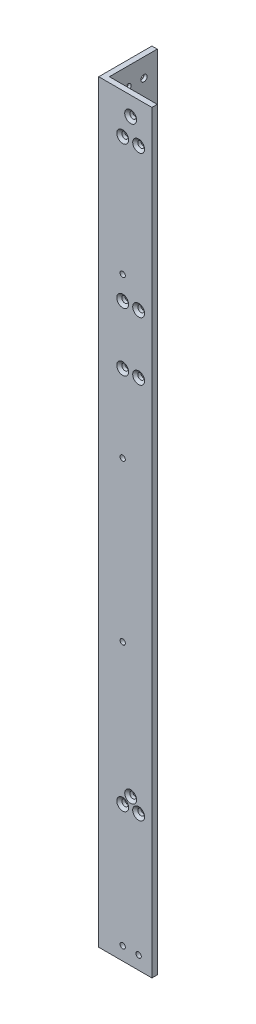
SolidWorks part; units mm, degrees
ref_plane "Front Plane" through (0, 0, 0) normal (0, 0, 1) x (1, 0, 0)
ref_plane "Top Plane" through (0, 0, 0) normal (0, 1, 0) x (1, 0, 0)
ref_plane "Right Plane" through (0, 0, 0) normal (1, 0, 0) x (0, 0, -1)
sketch "Sketch2" plane through (0, 0, 0) normal (0, 1, 0) x (1, 0, 0)
  line L0 (0, 31.75) -> (3.175, 31.75)
  line L1 (3.175, 31.75) -> (3.175, 3.175)
  line L2 (3.175, 3.175) -> (31.75, 3.175)
  line L3 (31.75, 3.175) -> (31.75, 0)
  line L4 (31.75, 0) -> (0, 0)
  line L5 (0, 0) -> (0, 31.75)
  point P9 (1.5875, 31.75)
  point P10 (31.75, 1.5875)
  dimension "D4" = 3.175
  dimension "D1" = 31.75
  dimension "D2" = 31.75
  dimension "D3" = 3.175
extrude "Boss-Extrude1" add sketch "Sketch2" along normal blind 450
sketch "LeftSideHoles-Sketch3" plane through (0, 0, 0) normal (0, 0, 1) x (1, 0, 0)
  line L0 (0, 0) -> (31.75, 0) construction
  line L1 (0, 450) -> (31.75, 450) construction
  line L3 (0, 450) -> (0, 0) construction
  circle A0 centre (14.2875, 81.1125) radius 1.5875
  circle A1 centre (23.8125, 81.1125) radius 1.5875
  circle A3 centre (19.05, 87.4625) radius 1.5875
  circle A5 centre (14.2875, 426.1875) radius 1.5875
  circle A6 centre (19.05, 438.8875) radius 1.5875
  circle A7 centre (23.8125, 426.1875) radius 1.5875
  circle A10 centre (14.2875, 341.2474) radius 1.5875
  circle A11 centre (23.8125, 341.2474) radius 1.5875
  circle A12 centre (14.2875, 306.3224) radius 1.5875
  circle A13 centre (23.8125, 306.3224) radius 1.5875
  circle A14 centre (14.2875, 7.9375) radius 1.5875
  circle A15 centre (23.8125, 7.9375) radius 1.5875
  circle A16 centre (14.2875, 165) radius 1.5875
  circle A17 centre (14.2875, 260) radius 1.5875
  circle A18 centre (14.2875, 355) radius 1.5875
  point P14 (19.1491, 87.4625)
  point P15 (19.1491, 438.8875)
  point P24 (15.875, 0)
  dimension "D4" = 3.175
  dimension "D1" = 81.1125
  dimension "D2" = 14.2875
  dimension "D10" = 7.9375
  dimension "D7" = 34.925
  dimension "D3" = 9.525
  dimension "D11" = 341.2474
  dimension "D12" = 165
  dimension "D13" = 95
  dimension "D5" = 6.35
  dimension "D6" = 12.7
  dimension "D8" = 11.1125
  dimension "D9" = 95
  dimension "D14" = 19.05
sketch "BackSideHoles-Sketch4" plane through (0, 0, 0) normal (-1, 0, 0) x (0, 0, 1)
  line L0 (-31.75, 450) -> (0, 450) construction
  line L2 (0, 450) -> (0, 0) construction
  line L3 (-31.75, 0) -> (0, 0) construction
  circle A0 centre (-19.05, 81.1125) radius 1.5875
  circle A2 centre (-23.8125, 87.4625) radius 1.5875
  circle A3 centre (-14.2875, 87.4625) radius 1.5875
  circle A4 centre (-23.8125, 438.8875) radius 1.5875
  circle A5 centre (-14.2875, 438.8875) radius 1.5875
  circle A6 centre (-19.05, 426.1875) radius 1.5875
  circle A10 centre (-23.8125, 336.7474) radius 1.5875
  circle A11 centre (-14.2875, 336.7474) radius 1.5875
  circle A12 centre (-18.6887, 330.3974) radius 1.5875
  circle A14 centre (-14.2875, 165) radius 1.5875
  circle A15 centre (-14.2875, 260) radius 1.5875
  circle A17 centre (-23.8125, 7.9375) radius 1.5875
  circle A18 centre (-14.2875, 7.9375) radius 1.5875
  circle A19 centre (-14.2875, 355) radius 1.5875
  point P18 (-18.8056, 81.1125)
  point P19 (-19.077, 426.1875)
  point P26 (0, 0)
  point P27 (-18.6887, 330.3974)
  dimension "D4" = 3.175
  dimension "D2" = 14.2875
  dimension "D5" = 6.35
  dimension "D14" = 19.05
  dimension "D6" = 11.1125
  dimension "D8" = 6.35
  dimension "D7" = 12.7
  dimension "D1" = 336.7474
  dimension "D10" = 165
  dimension "D11" = 95
  dimension "D13" = 7.9375
  dimension "D3" = 81.1125
  dimension "D9" = 9.525
  dimension "D12" = 95
  dimension "D15" = 18.6887
extrude "LeftSideHoles-Cut-Extrude1" cut sketch "LeftSideHoles-Sketch3" against normal blind 3.175
extrude "BackSideHoles-Cut-Extrude2" cut sketch "BackSideHoles-Sketch4" against normal blind 3.175
sketch "Sketch5" plane through (0, 0, 0) normal (-1, 0, 0) x (0, 0, 1)
  point P0 (-14.2875, 438.8875)
  point P3 (-23.8125, 438.8875)
  point P6 (-19.05, 426.1875)
  point P9 (-18.6887, 330.3974)
  point P12 (-14.2875, 336.7474)
  point P15 (-23.8125, 336.7474)
  point P18 (-19.05, 81.1125)
  point P21 (-14.2875, 87.4625)
  point P24 (-23.8125, 87.4625)
hole_wizard "CSK for #6 Flat Head Machine Screw (100)1" positions "Sketch5" profile "Sketch6" countersink size "#6" standard "ANSI Inch" end condition through all
sketch "Sketch6" plane through (0, 438.8875, -14.2875) normal (0, 1, 0) x (0, 0, 1)
  line L0 (0, 0) -> (0, 31.75)
  line L1 (0, 31.75) -> (1.8986, 31.75)
  line L2 (1.8986, 31.75) -> (1.8986, 1.38)
  line L3 (1.8986, 1.38) -> (3.5433, 0)
  line L5 (3.5433, 0) -> (0, 0)
  line L6 (-1.8986, 1.38) -> (-3.5433, 0) construction
  line L11 (0, -6.35) -> (0, 107.95) construction
  dimension "Thru Hole Dia." = 3.7973
  dimension "Thru Hole Depth" = 31.75
  dimension "Near C'Sink Dia." = 7.0866
  dimension "Near C'Sink Angle" = 100
sketch "Sketch8" plane through (0, 0, 0) normal (0, 0, 1) x (1, 0, 0)
  point P0 (19.05, 438.8875)
  point P3 (14.2875, 426.1875)
  point P6 (23.8125, 426.1875)
  point P9 (23.8125, 341.2474)
  point P12 (14.2875, 341.2474)
  point P15 (14.2875, 306.3224)
  point P18 (23.8125, 306.3224)
  point P21 (19.05, 87.4625)
  point P24 (14.2875, 81.1125)
  point P27 (23.8125, 81.1125)
hole_wizard "CSK for #6 Flat Head Machine Screw (100)2" positions "Sketch8" profile "Sketch9" countersink size "#6" standard "ANSI Inch" end condition through all
sketch "Sketch9" plane through (19.05, 438.8875, 0) normal (1, 0, 0) x (0, -1, 0)
  line L0 (0, 0) -> (0, 31.75)
  line L1 (0, 31.75) -> (1.8986, 31.75)
  line L2 (1.8986, 31.75) -> (1.8986, 1.38)
  line L3 (1.8986, 1.38) -> (3.5433, 0)
  line L5 (3.5433, 0) -> (0, 0)
  line L6 (-1.8986, 1.38) -> (-3.5433, 0) construction
  line L11 (0, -6.35) -> (0, 107.95) construction
  dimension "Thru Hole Dia." = 3.7973
  dimension "Thru Hole Depth" = 31.75
  dimension "Near C'Sink Dia." = 7.0866
  dimension "Near C'Sink Angle" = 100
equation "\"RailThickness\"= .125in'Spec"
equation "\"VSWidth\"= 1.25in'Spec"
equation "\"VSHeight\"= 1.25in'Spec"
equation "\"VSLength\"= 450mm"
equation "\"HoleOffsetFromEdge\"= \"RailThickness\" * 2.5"
equation "\"HoleOffsetFromSide\"= \"RailThickness\" * 3.5"
equation "\"LegHeight\"= 70mm'Space needed for PSU/Stepper/Electronics"
equation "\"VSBottomSideRailHoleY1FromBottomOfLowerRail\"= \"V1 BottomOfLowerRail\" + \"HoleOffsetFromSide\"'Equals 81.1125"
equation "\"VSSideRailHoleX1FromSide\"= \"HoleOffsetFromSide\" + \"RailThickness\""
equation "\"FasteningHoleDiameter\"= .125in"
equation "\"VSBottomSideRailHoleY2FromY1\"= \"LowerRailHeight\" - \"HoleOffsetFromSide\" - \"HoleOffsetFromEdge\"'Equals 6.35"
equation "\"VSTopSideRailHoleY1FromEdge\"= \"HoleOffsetFromEdge\" + \"RailThickness\""
equation "\"D4@LeftSideHoles-Sketch3\"=\"FasteningHoleDiameter\""
equation "\"D1@LeftSideHoles-Sketch3\"=\"VSBottomSideRailHoleY1FromBottomOfLowerRail\""
equation "\"D2@LeftSideHoles-Sketch3\"=\"VSSideRailHoleX1FromSide\""
equation "\"D1@Boss-Extrude1\"=\"VSLength\""
equation "\"D4@BackSideHoles-Sketch4\" = \"FasteningHoleDiameter\""
equation "\"VSMidSideRailHoleY1FromV8TopOfMidSideRail\"= \"V8 ToTopOfMidSideRail\" - \"HoleOffsetFromEdge\"'Equals 341.24737"
equation "\"LowerRailHeight\"= 1.00in"
equation "\"D1@Sketch2\"=\"VSHeight\""
equation "\"D2@Sketch2\"=\"VSWidth\""
equation "\"MidBackRailHeight\"= 1.00in"
equation "\"VSMidBackRailHoleY1FromV7TopOfMidBackRail\"= \"V7 ToTopOfMidBackRail\" - \"HoleOffsetFromEdge\"'Equals 339.64737"
equation "\"TopRailHeight\"= 1.25in"
equation "\"MidLeftOrRightSideRailHeight\"= 2.0in"
equation "\"D10@LeftSideHoles-Sketch3\"=\"HoleOffsetFromEdge\""
equation "\"VSMidBackRailHoleY2FromY1\"= \"MidBackRailHeight\" - \"HoleOffsetFromSide\" - \"HoleOffsetFromEdge\"'Equals 6.35"
equation "\"VSMidSideRailHoleY2FromY1\"= \"MidLeftOrRightSideRailHeight\" - \"HoleOffsetFromEdge\" * 2'Equals 34.925"
equation "\"D7@LeftSideHoles-Sketch3\"=\"VSMidSideRailHoleY2FromY1\""
equation "\"D8@BackSideHoles-Sketch4\"=\"VSMidBackRailHoleY2FromY1\""
equation "\"D6@BackSideHoles-Sketch4\"=\"VSTopSideRailHoleY1FromEdge\""
equation "\"VSTopSideRailHoleY2FromY1\"= \"TopRailHeight\" - \"VSTopSideRailHoleY1FromEdge\" - \"HoleOffsetFromEdge\"'Equals 12.7"
equation "\"D7@BackSideHoles-Sketch4\"=\"VSTopSideRailHoleY2FromY1\""
equation "\"VSBottomSideRailHoleX2FromX1\"= \"VSWidth\" - \"VSSideRailHoleX1FromSide\" - \"HoleOffsetFromEdge\""
equation "\"D3@LeftSideHoles-Sketch3\"=\"VSBottomSideRailHoleX2FromX1\""
equation "\"V1 BottomOfLowerRail\"= \"LegHeight\""
equation "\"StepperShaftLength\"= 24mm'Pulley will be attached to the end"
equation "\"ZAxisLeadScrewLength\"= 200mm"
equation "\"LM8UUHeight\"= 24mm'Spec"
equation "\"V2 ToBedAtTopOfZAxis\"= \"V1 BottomOfLowerRail\" - \"LowerEnclosureThickness\" + \"StepperShaftLength\" + \"ZAxisLeadScrewLength\" - \"LM8UUHeight\" / 2'Equals 277"
equation "\"HotEndToTopOfXAxisGB\"= 71.68487mm'Equals 71.68487. Measured after installed onto X-Axis linear rail guide block"
equation "\"TopOfGBToBottomOfLinearRail\"= \"LinearGBWidth\" / 2 + \"LinearRailWidth\" / 2'Equals 19.5"
equation "\"LinearGBWidth\"= 27mm'Spec"
equation "\"V5 ToBottomOfXAxisLinearRail\"= \"V4 ToTopOfBuildPlate/HotEndTip\" + \"HotEndToTopOfXAxisGB\" - \"TopOfGBToBottomOfLinearRail\"'Equals 352.18487"
equation "\"LinearRailWidth\"= 12mm'Spec"
equation "\"GABUpperHeight\"= 4mm"
equation "\"GABMidWallHeight\"= 28mm'Must equal 28 or changes alignment"
equation "\"V7 ToBottomOfMidBackRail\"=   \"V5 ToBottomOfXAxisLinearRail\" - \"GABUpperHeight\" - \"GABMidShortRiserHeight\" + \"GABRiserBossOffset\" - \"StepperShaftLength\"'Equals 319.28487"
equation "\"D1@BackSideHoles-Sketch4\" = \"VSMidBackRailHoleY1FromV7TopOfMidBackRail\""
equation "\"D11@LeftSideHoles-Sketch3\"=\"VSMidSideRailHoleY1FromV8TopOfMidSideRail\""
equation "\"V4 ToTopOfBuildPlate/HotEndTip\"= \"V2 ToBedAtTopOfZAxis\" + \"BedToBuildPlateStandoffLength\" + \"BuildPlateHeight\""
equation "\"BedToBuildPlateStandoffLength\"= 15mm"
equation "\"BuildPlateHeight\"= 8mm'Spec"
equation "\"V8 ToTopOfMidSideRail\"= \"V6 ToMiddleOfYAxisGantryBlock\" + \"MidSideRailVerticalOffset\"'Equals 349.18487"
equation "\"VSEnclosureOffsets\"= ( \"VSLength\" - \"LegHeight\" ) / 4"
equation "\"D12@LeftSideHoles-Sketch3\"=\"LegHeight\" + \"VSEnclosureOffsets\""
equation "\"D13@LeftSideHoles-Sketch3\"=\"VSEnclosureOffsets\""
equation "\"D10@BackSideHoles-Sketch4\"=\"LegHeight\" + \"VSEnclosureOffsets\""
equation "\"D11@BackSideHoles-Sketch4\"=\"VSEnclosureOffsets\""
equation "\"D13@BackSideHoles-Sketch4\"=\"HoleOffsetFromEdge\""
equation "\"D5@BackSideHoles-Sketch4\"=\"VSBottomSideRailHoleY2FromY1\""
equation "\"D3@BackSideHoles-Sketch4\"=\"VSBottomSideRailHoleY1FromBottomOfLowerRail\""
equation "\"D2@BackSideHoles-Sketch4\"=\"VSSideRailHoleX1FromSide\""
equation "\"D5@LeftSideHoles-Sketch3\"=\"VSBottomSideRailHoleY2FromY1\""
equation "\"D6@LeftSideHoles-Sketch3\"=\"VSTopSideRailHoleY2FromY1\""
equation "\"D8@LeftSideHoles-Sketch3\"=\"VSTopSideRailHoleY1FromEdge\""
equation "\"LowerEnclosureThickness\"= 5mm"
equation "\"V7 ToTopOfMidBackRail\"= \"V7 ToBottomOfMidBackRail\" + \"MidBackRailHeight\""
equation "\"GABHeight\"= \"GABLowerHeight\" + \"GABMidWallHeight\" + \"GABUpperHeight\""
equation "\"GABLowerHeight\"= 4mm"
equation "\"V6 ToMiddleOfYAxisGantryBlock\"= \"V5 ToBottomOfXAxisLinearRail\" - \"GABHeight\" / 2'Equals 334.18487"
equation "\"D9@LeftSideHoles-Sketch3\"=\"VSEnclosureOffsets\""
equation "\"D12@BackSideHoles-Sketch4\"=\"VSEnclosureOffsets\""
equation "\"MidSideRailVerticalOffset\"= \"LinearRailWidth\" + 3mm'Allows space for RodStabilizer to attach to bottom of MidSideRail"
equation "\"GABRiserBossOffset\"= 0.4mm'Aligns Pulleys inside edges to be 2.5mm (.5mm apart top to bottom)"
equation "\"GABMidShortRiserHeight\"= \"GABMidWallHeight\" / 2 - \"20TGT2PulleyWidth\"'Equals 5.3"
equation "\"20TGT2PulleyWidth\"= 8.7mm'The STL of the Pulley in the diagram is a bit larger"
equation "\"VSMidSideRailHoleXFromSideToCenter\"= \"RailThickness\" * 6"
equation "\"D14@LeftSideHoles-Sketch3\"=\"VSMidSideRailHoleXFromSideToCenter\""
equation "\"D14@BackSideHoles-Sketch4\"=\"VSMidSideRailHoleXFromSideToCenter\""
equation "\"D9@BackSideHoles-Sketch4\"=\"VSBottomSideRailHoleX2FromX1\""
